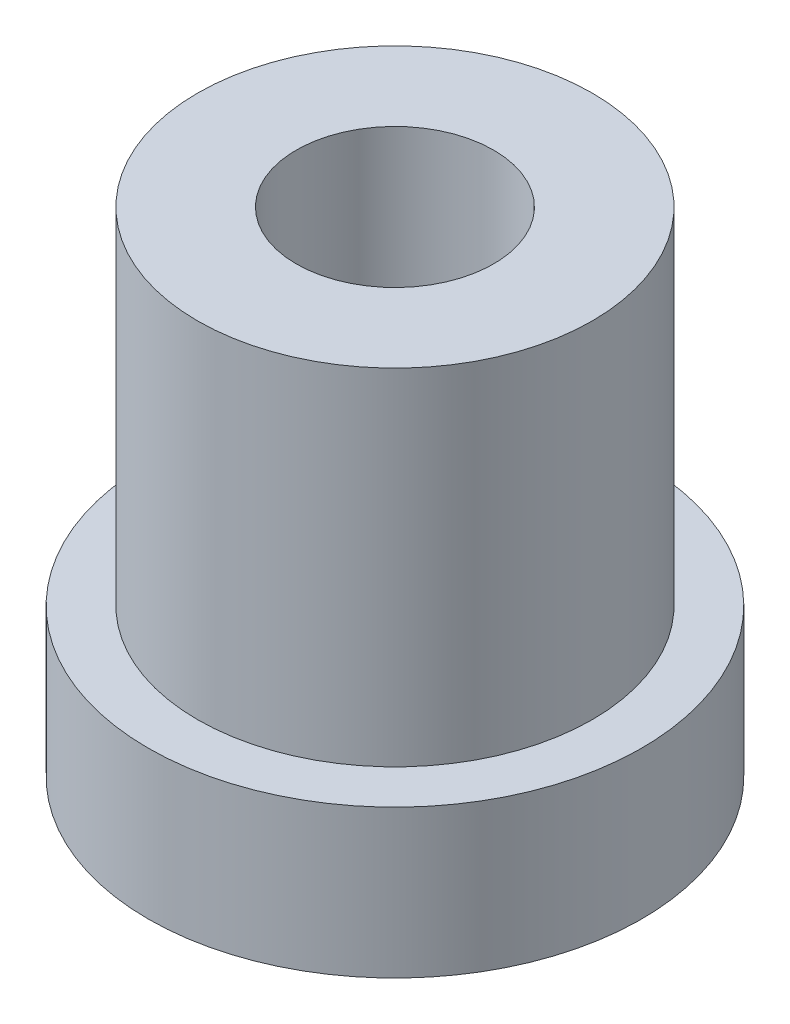
SolidWorks part; units mm, degrees
ref_plane "Front Plane" through (0, 0, 0) normal (0, 0, 1) x (1, 0, 0)
ref_plane "Top Plane" through (0, 0, 0) normal (0, 1, 0) x (1, 0, 0)
ref_plane "Right Plane" through (0, 0, 0) normal (1, 0, 0) x (0, 0, -1)
sketch "Sketch2" plane through (0, 0, 0) normal (0, 1, 0) x (1, 0, 0)
  circle A0 centre (0, 0) radius 8
  dimension "D1" = 16
extrude "Boss-Extrude1" add sketch "Sketch2" along normal blind 20
sketch "Sketch3" plane through (0, 0, 0) normal (0, 1, 0) x (1, 0, 0)
  circle A0 centre (0, 0) radius 10
  dimension "D1" = 20
extrude "Boss-Extrude2" add sketch "Sketch3" along normal blind 6
sketch "Sketch1" plane through (0, 0, 0) normal (0, 1, 0) x (1, 0, 0)
  circle A0 centre (0, 0) radius 4
  dimension "D1" = 8
extrude "Cut-Extrude1" cut sketch "Sketch1" along normal through all
